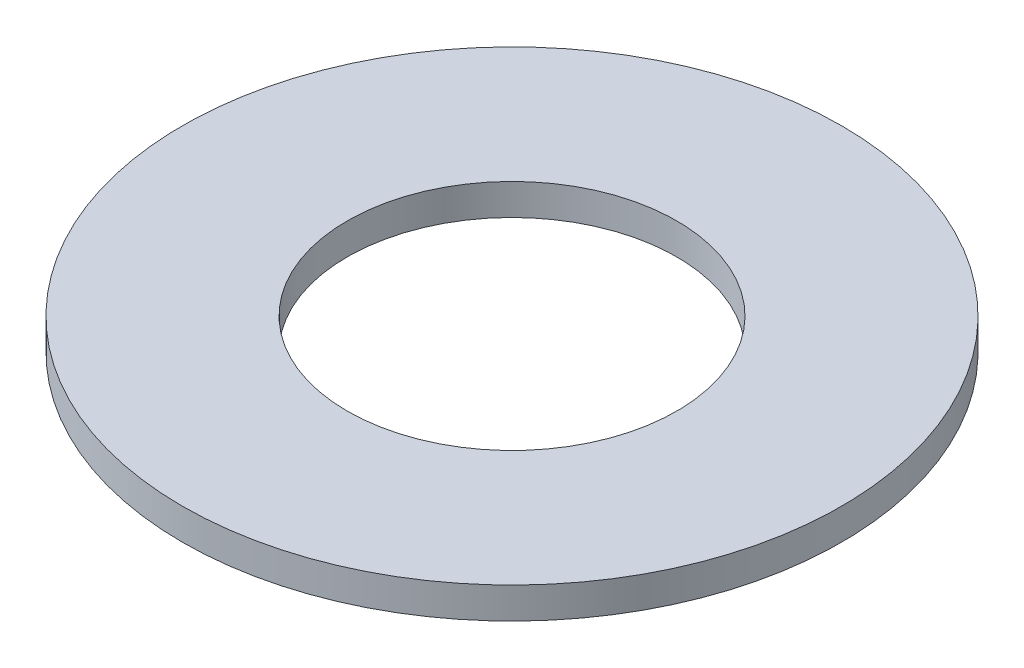
SolidWorks part; units mm, degrees
ref_plane "Front Plane" through (0, 0, 0) normal (0, 0, 1) x (1, 0, 0)
ref_plane "Top Plane" through (0, 0, 0) normal (0, 1, 0) x (1, 0, 0)
ref_plane "Right Plane" through (0, 0, 0) normal (1, 0, 0) x (0, 0, -1)
sketch "Sketch1" plane through (0, 0, 0) normal (0, 1, 0) x (1, 0, 0)
  circle A0 centre (0, 0) radius 95
  dimension "FLANGE_OD" = 190
extrude "Boss-Extrude1" add sketch "Sketch1" along normal blind 9
sketch "Sketch2" plane through (0, 0, 0) normal (0, 1, 0) x (1, 0, 0)
  circle A0 centre (0, 0) radius 47.5
  dimension "BORE_D" = 95
extrude "Cut-Extrude1" cut sketch "Sketch2" along normal through all
sketch "Sketch3" plane through (0, 9, 0) normal (0, 1, 0) x (1, 0, 0)
  circle A0 centre (0, 0) radius 44.27 construction
  circle A1 centre (-44.27, 0) radius 2.4835
  dimension "BOLT_D" = 4.9671
  dimension "BOLT_PCD" = 88.5401
extrude "Cut-Extrude2" cut sketch "Sketch3" against normal blind 8.6935 rebuild error yes
pattern_circular "CirPattern1" count 5 over 360 rebuild error yes
